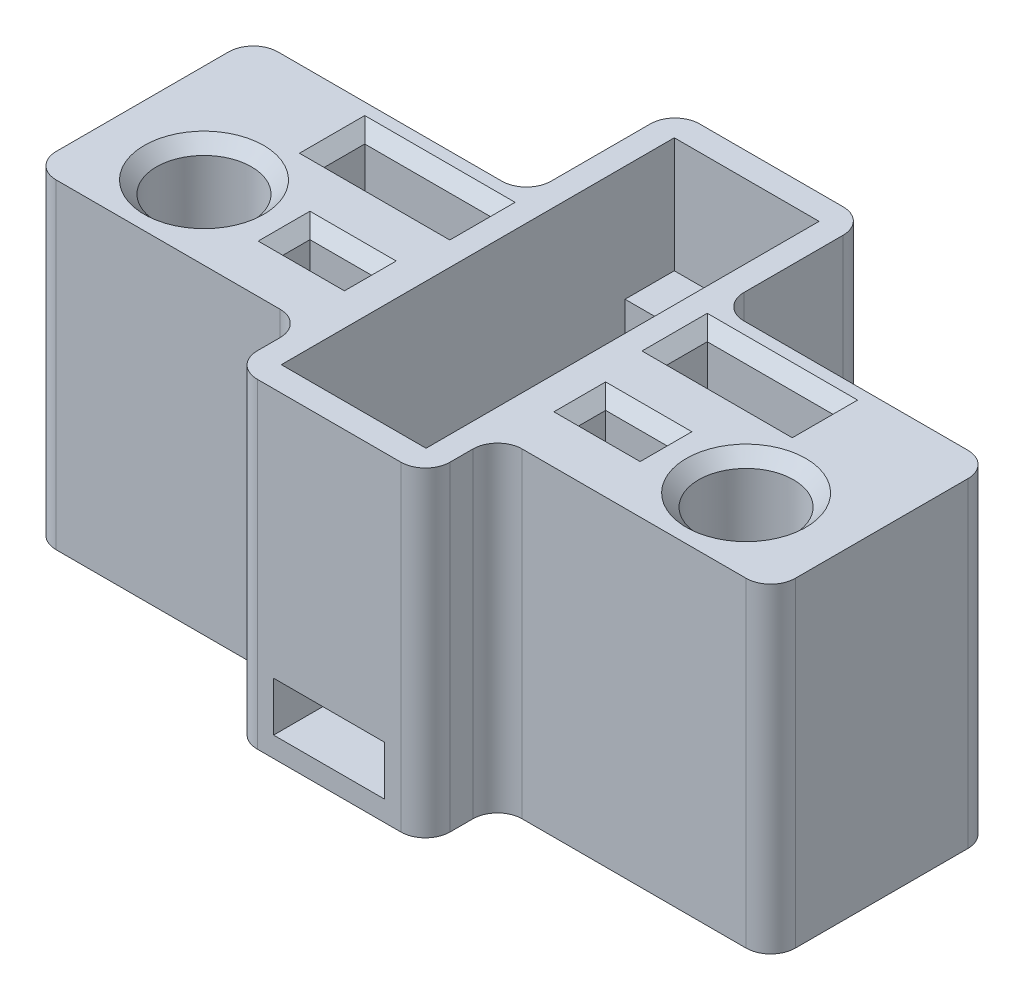
SolidWorks part; units mm, degrees
ref_plane "Front Plane" through (0, 0, 0) normal (0, 0, 1) x (1, 0, 0)
ref_plane "Top Plane" through (0, 0, 0) normal (0, 1, 0) x (1, 0, 0)
ref_plane "Right Plane" through (0, 0, 0) normal (1, 0, 0) x (0, 0, -1)
sketch "Sketch1" plane through (0, 0, 0) normal (0, 1, 0) x (1, 0, 0)
  line L1 (-30, -9) -> (30, -9)
  line L2 (-30, -9) -> (-30, 9)
  line L3 (-30, 9) -> (30, 9)
  line L4 (30, -9) -> (30, 9)
  line L5 (-30, -9) -> (30, 9) construction
  line L6 (-30, 9) -> (30, -9) construction
  point P0 (0, 0)
  dimension "D1" = 60
  dimension "D2" = 18
extrude "Boss-Extrude1" add sketch "Sketch1" along normal blind 26
sketch "Sketch2" plane through (0, 26, 0) normal (0, 1, 0) x (1, 0, 0)
  line L0 (0, 0) -> (0, -9) construction
  line L1 (-30, -9) -> (30, -9) construction
  circle A0 centre (-22, -3) radius 3.85
  circle A1 centre (22, -3) radius 3.85
  dimension "D1" = 7.7
  dimension "D2" = 7.7
  dimension "D3" = 44
  dimension "D4" = 22
  dimension "D5" = 6
  dimension "D6" = 6
extrude "Eyeshaft holes" cut sketch "Sketch2" against normal blind 15
fillet "Eyeshaft Fillet" radius 3 2 edges at (22, 11, 6.85) (-22, 11, 6.85)
sketch "Sketch5" plane through (0, 26, 0) normal (0, 1, 0) x (1, 0, 0)
  line L0 (-22, -3) -> (22, -3) construction
  line L2 (-14.5, -4.1) -> (-9.5, -4.1)
  line L3 (-14.5, -4.1) -> (-14.5, -1.9)
  line L4 (-14.5, -1.9) -> (-9.5, -1.9)
  line L5 (-9.5, -4.1) -> (-9.5, -1.9)
  line L6 (-14.5, -4.1) -> (-9.5, -1.9) construction
  line L7 (-14.5, -1.9) -> (-9.5, -4.1) construction
  line L8 (9.5, -4.1) -> (14.5, -4.1)
  line L9 (9.5, -4.1) -> (9.5, -1.9)
  line L10 (9.5, -1.9) -> (14.5, -1.9)
  line L11 (14.5, -4.1) -> (14.5, -1.9)
  line L12 (9.5, -4.1) -> (14.5, -1.9) construction
  line L13 (9.5, -1.9) -> (14.5, -4.1) construction
  point P4 (-12, -3)
  point P9 (12, -3)
  dimension "D1" = 2.2
  dimension "D2" = 5
  dimension "D3" = 5
  dimension "D4" = 2.2
  dimension "D5" = 10
  dimension "D6" = 10
extrude "Front leg holes" cut sketch "Sketch5" against normal blind 13
sketch "Sketch7" plane through (0, 26, 0) normal (0, 1, 0) x (1, 0, 0)
  line L1 (-19, 7.05) -> (-8.8, 7.05)
  line L2 (-19, 7.05) -> (-19, 3.75)
  line L3 (-19, 3.75) -> (-8.8, 3.75)
  line L4 (-8.8, 7.05) -> (-8.8, 3.75)
  line L5 (8.8, 7.05) -> (19, 7.05)
  line L6 (8.8, 7.05) -> (8.8, 3.75)
  line L7 (8.8, 3.75) -> (19, 3.75)
  line L8 (19, 7.05) -> (19, 3.75)
  circle A0 centre (-22, -3) radius 3.85 construction
  circle A2 centre (22, -3) radius 3.85 construction
  point P16 (-20.2379, 3.75)
  dimension "D1" = 3.3
  dimension "D2" = 10.2
  dimension "D3" = 10.2
  dimension "D4" = 3.3
  dimension "D5" = 10.05
  dimension "D6" = 10.05
  dimension "D7" = 3
  dimension "D8" = 3
extrude "Back Legs" cut sketch "Sketch7" against normal blind 13
sketch "Sketch18" plane through (0, 26, 0) normal (0, 1, 0) x (1, 0, 0)
  line L0 (0, 9) -> (0, -9) construction
  line L1 (30, 9) -> (-30, 9) construction
  line L2 (-30, -9) -> (30, -9) construction
  line L3 (-22, -3) -> (22, -3) construction
  line L4 (-7.825, -14.85) -> (7.825, -14.85)
  line L5 (-7.825, -14.85) -> (-7.825, 21.05)
  line L6 (-7.825, 21.05) -> (7.825, 21.05)
  line L7 (7.825, -14.85) -> (7.825, 21.05)
  line L8 (-7.825, -14.85) -> (7.825, 21.05) construction
  line L9 (-7.825, 21.05) -> (7.825, -14.85) construction
  point P6 (0, 3.1)
  dimension "D1" = 24.05
  dimension "D2" = 11.85
  dimension "D3" = 15.65
extrude "Boss-Extrude2" add sketch "Sketch18" against normal up to surface (26 mm away) up to face at (0, 0, 0)
sketch "Sketch19" plane through (0, 26, 0) normal (0, 1, 0) x (1, 0, 0)
  line L0 (0, 21.05) -> (0, -14.85) construction
  line L1 (7.825, 21.05) -> (-7.825, 21.05) construction
  line L2 (-7.825, -14.85) -> (7.825, -14.85) construction
  line L3 (-22, -3) -> (22, -3) construction
  line L5 (-5.875, -12.85) -> (5.875, -12.85)
  line L6 (-5.875, -12.85) -> (-5.875, 19.05)
  line L7 (-5.875, 19.05) -> (5.875, 19.05)
  line L8 (5.875, -12.85) -> (5.875, 19.05)
  line L9 (-5.875, -12.85) -> (5.875, 19.05) construction
  line L10 (-5.875, 19.05) -> (5.875, -12.85) construction
  point P10 (0, 3.1)
  dimension "D1" = 22.05
  dimension "D2" = 9.85
  dimension "D3" = 11.75
extrude "Cut-Extrude9" cut sketch "Sketch19" against normal blind 9.35
sketch "Sketch20" plane through (0, 16.65, 0) normal (0, 1, 0) x (1, 0, 0)
  line L0 (-22, -3) -> (22, -3) construction
  line L1 (0, -12.85) -> (0, 19.05) construction
  line L2 (-5.875, -12.85) -> (5.875, -12.85) construction
  line L3 (5.875, 19.05) -> (-5.875, 19.05) construction
  line L5 (-5.875, 15.05) -> (5.875, 15.05)
  line L6 (-5.875, 15.05) -> (-5.875, -8.85)
  line L7 (-5.875, -8.85) -> (5.875, -8.85)
  line L8 (5.875, 15.05) -> (5.875, -8.85)
  line L9 (-5.875, 15.05) -> (5.875, -8.85) construction
  line L10 (-5.875, -8.85) -> (5.875, 15.05) construction
  point P10 (0, 3.1)
  dimension "D1" = 5.85
  dimension "D2" = 18.05
  dimension "D3" = 11.75
extrude "Cut-Extrude10" cut sketch "Sketch20" against normal blind 15
sketch "Sketch15" [suppressed] plane through (0, 0, 17.5) normal (0, 0, 1) x (1, 0, 0)
  line L0 (0, 0) -> (0, 26) construction
  line L1 (-10, 0) -> (10, 0) construction
  line L2 (10, 26) -> (-10, 26) construction
  line L4 (-4.5, 1.4) -> (4.5, 1.4)
  line L5 (-4.5, 1.4) -> (-4.5, 5.4)
  line L6 (-4.5, 5.4) -> (4.5, 5.4)
  line L7 (4.5, 1.4) -> (4.5, 5.4)
  line L8 (-4.5, 1.4) -> (4.5, 5.4) construction
  line L9 (-4.5, 5.4) -> (4.5, 1.4) construction
  point P6 (0, 3.4)
  dimension "D1" = 9
  dimension "D2" = 4
  dimension "D3" = 1.4
sketch "Sketch16" [suppressed] plane through (0, 12.4, 0) normal (0, 1, 0) x (1, 0, 0)
  line L0 (-6.1, -12) -> (6.1, -12) construction
  line L1 (-2.5, -12.5) -> (2.5, -12.5)
  line L2 (-2.5, -12.5) -> (-2.5, -11.5)
  line L3 (-2.5, -11.5) -> (2.5, -11.5)
  line L4 (2.5, -12.5) -> (2.5, -11.5)
  line L5 (-2.5, -12.5) -> (2.5, -11.5) construction
  line L6 (-2.5, -11.5) -> (2.5, -12.5) construction
  point P0 (0, -12)
  dimension "D1" = 5
  dimension "D2" = 1
sketch "Sketch13" [suppressed] plane through (0, 12.4, 0) normal (0, 1, 0) x (1, 0, 0)
  line L1 (6.1, 13) -> (6.1, 16.6) construction
  line L2 (6.1, 13) -> (-6.1, 13) construction
  line L4 (6.1, -16.6) -> (6.1, -12) construction
  line L5 (-2.5, -12.5) -> (2.5, -12.5) construction
  circle A0 centre (0.1, 15) radius 0.5
  circle A1 centre (0.1, -14.5) radius 0.5
  dimension "D2" = 6
  dimension "D3" = 1
  dimension "D4" = 1
  dimension "D1" = 2
  dimension "D5" = 2
  dimension "D6" = 6
fillet "Fillet3" [suppressed] radius 2
sketch "Sketch17" plane through (0, 26, 0) normal (0, 1, 0) x (1, 0, 0)
  line L1 (-5.9, -16.2) -> (5.9, -16.2)
  line L2 (-5.9, -16.2) -> (-5.9, 16.2)
  line L3 (-5.9, 16.2) -> (5.9, 16.2)
  line L4 (5.9, -16.2) -> (5.9, 16.2)
  line L5 (-5.9, -16.2) -> (5.9, 16.2) construction
  line L6 (-5.9, 16.2) -> (5.9, -16.2) construction
  point P0 (0, 0)
  dimension "D1" = 11.8
  dimension "D2" = 32.4
extrude "Servo Body" [suppressed] cut sketch "Sketch17" against normal blind 24
ref_axis "Axis1" through (-22, 14, 3) along (0, 1, 0)
ref_axis "Axis2" through (22, 14, 3) along (0, 1, 0)
ref_plane "Plane2" through (0, 0, 3) normal (0, 0, 1) x (1, 0, 0)
fillet "Fillet4" radius 2 12 edges at (7.825, 13, -9) (7.825, 13, -21.05) (30, 13, -9) (30, 13, 9) (7.825, 13, 9) (7.825, 13, 14.85) (-7.825, 13, 14.85) (-7.825, 13, 9) (-30, 13, 9) (-30, 13, -9) (-7.825, 13, -9) (-7.825, 13, -21.05)
chamfer "Chamfer1" distance 1 angle 45 18 edges at (22, 26, 6.85) (-22, 26, 6.85) (-14.5, 26, 3) (-12, 26, 4.1) (-12, 26, 1.9) (-9.5, 26, 3) (14.5, 26, 3) (12, 26, 4.1) (9.5, 26, 3) (12, 26, 1.9) (19, 26, -5.4) (13.9, 26, -3.75) (8.8, 26, -5.4) (13.9, 26, -7.05) (-8.8, 26, -5.4) (-13.9, 26, -3.75) (-19, 26, -5.4) (-13.9, 26, -7.05)
sketch "Sketch21" plane through (0, 0, 8.85) normal (0, 0, -1) x (-1, 0, 0)
  line L0 (0, 1.65) -> (0, 16.65) construction
  line L1 (5.875, 1.65) -> (-5.875, 1.65) construction
  line L2 (5.875, 16.65) -> (-5.875, 16.65) construction
  line L3 (4.5, 5.65) -> (-4.5, 5.65)
  line L4 (4.5, 5.65) -> (4.5, 1.65)
  line L5 (-4.5, 5.65) -> (-4.5, 1.65)
  line L6 (4.5, 1.65) -> (-4.5, 1.65)
  line L7 (4.5, 5.65) -> (-4.5, 1.65) construction
  line L8 (-4.5, 5.65) -> (4.5, 1.65) construction
  point P7 (0, 3.65)
  dimension "D1" = 9
  dimension "D2" = 0
  dimension "D3" = 4
  dimension "D4" = 0
extrude "Cut-Extrude11" cut sketch "Sketch21" against normal blind 15
fillet "Fillet5" radius 2 1 edges at (0, 5.65, 8.85)
sketch "Sketch22" plane through (0, 16.65, 0) normal (0, 1, 0) x (1, 0, 0)
  line L0 (5.875, 15.05) -> (-5.875, 15.05) construction
  line L1 (-5.875, -8.85) -> (5.875, -8.85) construction
  circle A0 centre (0, 17.3) radius 0.75
  circle A1 centre (0, -11.1) radius 0.75
  dimension "D1" = 2.25
  dimension "D2" = 1.5
  dimension "D3" = 1.5
  dimension "D4" = 2.25
extrude "Cut-Extrude12" cut sketch "Sketch22" against normal blind 3
